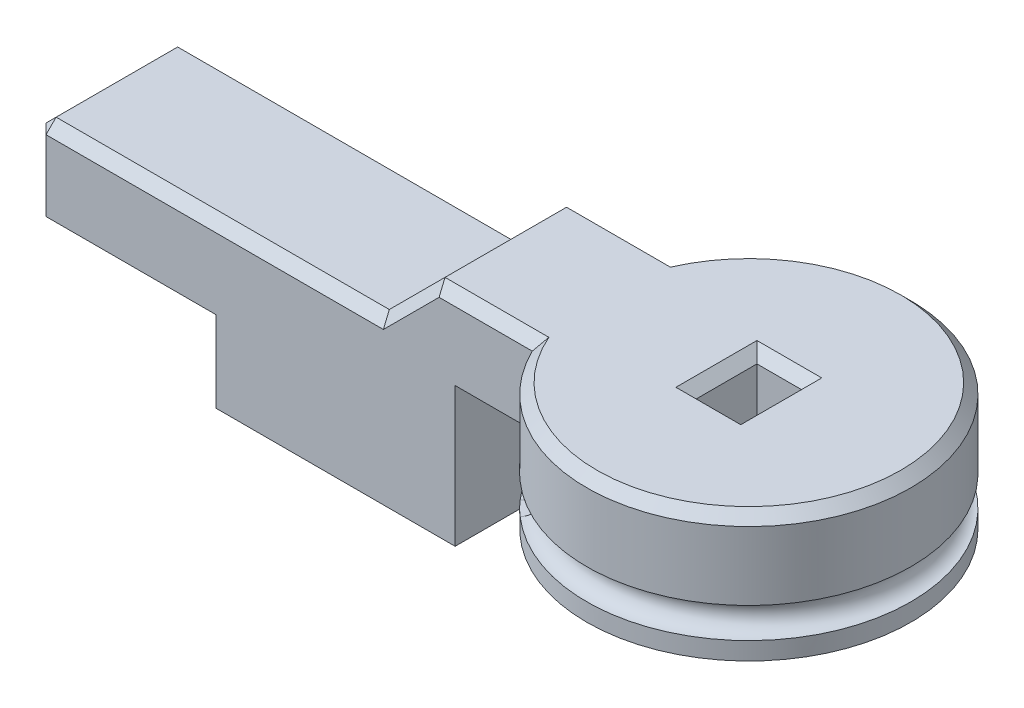
SolidWorks part; units mm, degrees
ref_plane "Front Plane" through (0, 0, 0) normal (0, 0, 1) x (1, 0, 0)
ref_plane "Top Plane" through (0, 0, 0) normal (0, 1, 0) x (1, 0, 0)
ref_plane "Right Plane" through (0, 0, 0) normal (1, 0, 0) x (0, 0, -1)
sketch "Sketch1" plane through (0, 0, 0) normal (0, 1, 0) x (1, 0, 0)
  line L0 (-1.1, 1.0198) -> (-1.1, -1.0198)
  line L1 (1.1, 1.0198) -> (1.1, -1.0198)
  line L2 (-1.1, 1.0198) -> (-1.1, 1.5)
  line L3 (-1.1, 1.5) -> (1.1, 1.5)
  line L4 (1.1, 1.5) -> (1.1, 1.0198)
  line L5 (-1.1, -1.0198) -> (-1.1, -1.5)
  line L6 (-1.1, -1.5) -> (1.1, -1.5)
  line L7 (1.1, -1.5) -> (1.1, -1.0198)
  arc A0 (-1.1, -1.0198) -> (1.1, -1.0198) centre (0, 0) ccw construction
  circle A1 centre (0, 0) radius 8
  arc A2 (-1.1, 1.0198) -> (-1.1, -1.0198) centre (0, 0) ccw construction
  arc A3 (1.1, -1.0198) -> (1.1, 1.0198) centre (0, 0) ccw construction
  arc A4 (1.1, 1.0198) -> (-1.1, 1.0198) centre (0, 0) ccw construction
  dimension "D1" = 3
  dimension "D2" = 16
  dimension "D3" = 1.1
  dimension "D4" = 1.1
extrude "Boss-Extrude1" add sketch "Sketch1" along normal blind 3.25
sketch "Sketch2" plane through (0, 0, 0) normal (1, 0, 0) x (0, 0, -1)
  line L0 (8, 0) -> (8, 0.875) construction
  line L1 (8, 0) -> (8, 3.25) construction
  line L2 (8, 0.875) -> (8, 2.375)
  line L3 (8, 2.375) -> (8, 3.25) construction
  arc A0 (8, 0.875) -> (8, 2.375) centre (8, 1.625) cw
  dimension "D4" = 0.75
  dimension "D1" = 0.875
  dimension "D2" = 0.875
  dimension "D3" = 1.5
revolve "Cut-Revolve1" cut sketch "Sketch2" angle 360 about axis through (0, 3.25, 0) along (0, -1, 0)
sketch "Sketch3" plane through (0, 3.25, 0) normal (0, 1, 0) x (1, 0, 0)
  line L2 (-1003.4237, 3.5) -> (48996.5763, 3.5) construction
  line L3 (-1003.5923, -3.5) -> (48996.4077, -3.5) construction
  line L4 (-15, -998.2632) -> (-15, 49001.7368) construction
  line L5 (-15, 3.5) -> (-7.1937, 3.5)
  line L6 (-15, 3.5) -> (-15, -3.5)
  line L7 (-15, -3.5) -> (-7.1937, -3.5)
  line L8 (-1.1, 1.5) -> (-1.1, -1.5)
  line L9 (-1.1, 1.5) -> (1.1, 1.5)
  line L10 (1.1, -1.5) -> (1.1, 1.5)
  arc A0 (-7.1937, -3.5) -> (-7.1937, 3.5) centre (0, 0) ccw
  arc A5 (-7.1937, 3.5) -> (-7.1937, -3.5) centre (0, 0) ccw construction
  circle M2 centre (0, 0) radius 8
  line M3 (-1.1, -1.5) -> (-1.1, 1.5)
  line M5 (1.1, 1.5) -> (1.1, -1.5)
  line M17 (1.1, -1.5) -> (-1.1, -1.5)
  line M18 (-1.1, 1.5) -> (1.1, 1.5)
  dimension "D1" = 16
  dimension "D2" = 3.5
  dimension "D3" = 3.5
  dimension "D4" = 15
extrude "Boss-Extrude2" add sketch "Sketch3" along normal blind 3 contours M2 M5 M17 M3 M18 | L6 L7 L5 M2
sketch "Sketch4" plane through (0, 3.25, 0) normal (0, -1, 0) x (1, 0, 0)
  line L1 (-31.7, 3.5) -> (-11, 3.5)
  line L2 (-31.7, 3.5) -> (-31.7, -3.5)
  line L3 (-31.7, -3.5) -> (-11, -3.5)
  line L4 (-11, 3.5) -> (-11, -3.5)
  line L5 (-15, 3.5) -> (-7.1937, 3.5) construction
  line L6 (-15, -3.5) -> (-7.1937, -3.5) construction
  dimension "D1" = 11
  dimension "D2" = 31.7
extrude "Boss-Extrude3" add sketch "Sketch4" along normal blind 3.75 and the other way up to surface
sketch "Sketch6" plane through (0, 0, 0) normal (0, -1, 0) x (-1, 0, 0)
  line L0 (0, 0) -> (8, 0) construction
  line L1 (0, 0) -> (5.6569, -5.6569) construction
  line L2 (0, 0) -> (5.6569, 5.6569) construction
  line L3 (4, -4) -> (4, 4) construction
  line L4 (3.5, -4) -> (3.5, 4)
  line L5 (4.5, -4) -> (4.5, -2.7042)
  line L6 (4.5, -2.7042) -> (4.5, 0) construction
  line L7 (4.5, 2.7042) -> (4.5, 4)
  line L8 (4.5, 0) -> (4.5, 2.7042) construction
  circle A0 centre (0, 0) radius 8 construction
  arc A1 (3.5, -4) -> (4.5, -4) centre (4, -4) ccw
  arc A2 (4.5, 4) -> (3.5, 4) centre (4, 4) ccw
  arc A3 (3.6464, -3.6464) -> (3.5, -4) centre (4, -4) ccw construction
  arc A4 (4, -3.5) -> (3.6464, -3.6464) centre (4, -4) ccw construction
  arc A5 (4.5, -4) -> (4, -3.5) centre (4, -4) ccw construction
  arc A6 (3.6464, 3.6464) -> (4, 3.5) centre (4, 4) ccw construction
  arc A7 (4, 3.5) -> (4.5, 4) centre (4, 4) ccw construction
  arc A8 (3.5, 4) -> (3.6464, 3.6464) centre (4, 4) ccw construction
  arc A9 (4.5, -2.7042) -> (4.5, 2.7042) centre (0, 0) ccw
  dimension "D4" = 1
  dimension "D5" = 1
  dimension "D6" = 5.25
  dimension "D1" = 45
  dimension "D2" = 45
  dimension "D3" = 4
extrude "Cut-Extrude2" cut sketch "Sketch6" against normal blind 2.375
sketch3d "3DSketch1"
  line L0 (-5.6569, 0, 5.6569) -> (-5.6569, -2.945, 5.6569) construction
  line L1 (-5.6569, 0, -5.6569) -> (-5.6569, -2.5861, -5.6569) construction
  line L2 (-5.6569, 0, 5.6569) -> (-8.703, 0, 2.6108) construction
  line L3 (0, 0, 0) -> (-5.6569, 0, 5.6569) construction
  line L4 (-5.6569, 0, -5.6569) -> (-6.0039, 0, -5.3098) construction
  line L5 (0, 0, 0) -> (-5.6569, 0, -5.6569) construction
ref_plane "Plane1" through (-5.6569, 0, 5.6569) normal (-0.7071, 0, 0.7071) x (0.7071, 0, 0.7071)
ref_plane "Plane2" through (-5.6569, 0, -5.6569) normal (0.7071, 0, 0.7071) x (0.7071, 0, -0.7071)
sketch "Sketch7" plane through (-5.6569, 0, 5.6569) normal (-0.7071, 0, 0.7071) x (0.7071, 0, 0.7071)
  line L0 (0, -1000) -> (0, 49000) construction
  line L1 (-0.5, 0.875) -> (0.5, 0.875)
  line L2 (8, 0.875) -> (-8, 0.875) construction
  line L3 (-0.5, 0.875) -> (-0.5, 2.375)
  line L4 (-0.3536, 2.375) -> (-1.2698, 2.375) construction
  line L5 (-0.5, 2.375) -> (0.5, 2.375)
  line L6 (0.5, 2.375) -> (0.5, 0.875)
  point P8 (0, 0.875)
  dimension "D1" = 1
extrude "Cut-Extrude3" cut sketch "Sketch7" against normal up to surface (2.3431 mm away)
sketch "Sketch8" plane through (-5.6569, 0, -5.6569) normal (0.7071, 0, 0.7071) x (0.7071, 0, -0.7071)
  line L0 (0, -1000) -> (0, 49000) construction
  line L2 (-0.5, 0.875) -> (0.5, 0.875)
  line L3 (8, 0.875) -> (-7.9844, 0.875) construction
  line L4 (-0.5, 0.875) -> (-0.5, 2.375)
  line L5 (8, 2.375) -> (-7.9844, 2.375) construction
  line L6 (-0.5, 2.375) -> (0.5, 2.375)
  line L7 (0.5, 2.375) -> (0.5, 0.875)
  point P8 (0, 0.875)
  dimension "D1" = 1
extrude "Cut-Extrude4" cut sketch "Sketch8" along normal up to surface (2.3431 mm away)
sketch "Sketch9" plane through (0, 3.25, 0) normal (0, -1, 0) x (1, 0, 0)
  line L0 (-7.1937, -3.5) -> (-11, -3.5)
  line L2 (-11, -3.5) -> (-11, 3.5) construction
  line L3 (-7.1937, 3.5) -> (-11, 3.5)
  line L4 (-11, -3.5) -> (-11, 3.5)
  line L5 (-11, 0) -> (-8, 0) construction
  arc A0 (-7.1937, -3.5) -> (-7.1937, 3.5) centre (0, 0) cw
  dimension "D1" = 8
  dimension "D2" = 3.5
extrude "Boss-Extrude4" add sketch "Sketch9" along normal up to vertex (3.25 mm away)
sketch "Sketch11" plane through (0, -0.5, 0) normal (0, -1, 0) x (1, 0, 0)
  line L0 (-11, 3.5) -> (-31.7, 3.5) construction
  line L1 (-11, -3.5) -> (-22.8, -3.5)
  line L2 (-11, -3.5) -> (-11, 3.5)
  line L3 (-11, 3.5) -> (-22.8, 3.5)
  line L4 (-22.8, -3.5) -> (-22.8, 3.5)
  dimension "D1" = 11.8
extrude "Boss-Extrude5" add sketch "Sketch11" along normal blind 4
sketch "Sketch13" plane through (0, 6.25, 0) normal (0, 1, 0) x (1, 0, 0)
  line L0 (-31.7, 3.5) -> (-7.1937, 3.5) construction
  line L1 (-31.7, -3.5) -> (-12, -3.5)
  line L2 (-31.7, -3.5) -> (-31.7, 3.5)
  line L3 (-31.7, 3.5) -> (-12, 3.5)
  line L4 (-12, -3.5) -> (-12, 3.5)
  dimension "D1" = 12
extrude "Cut-Extrude6" cut sketch "Sketch13" against normal blind 2.75
chamfer "Chamfer2" distance 2.75 angle 45 1 edges at (-12, 3.5, 0)
chamfer "Chamfer1" distance 0.5 angle 45 14 edges at (8, 6.25, 0) (-9.5969, 6.25, 3.5) (-9.5969, 6.25, -3.5) (-31.7, 1.5, 3.5) (-31.7, 1.5, -3.5) (0, 6.25, 1.5) (0, 6.25, -1.5) (1.1, 6.25, 0) (-1.1, 6.25, 0) (-13.375, 4.875, 3.5) (-23.225, 3.5, 3.5) (-31.7, 3.5, 0) (-23.225, 3.5, -3.5) (-13.375, 4.875, -3.5)
